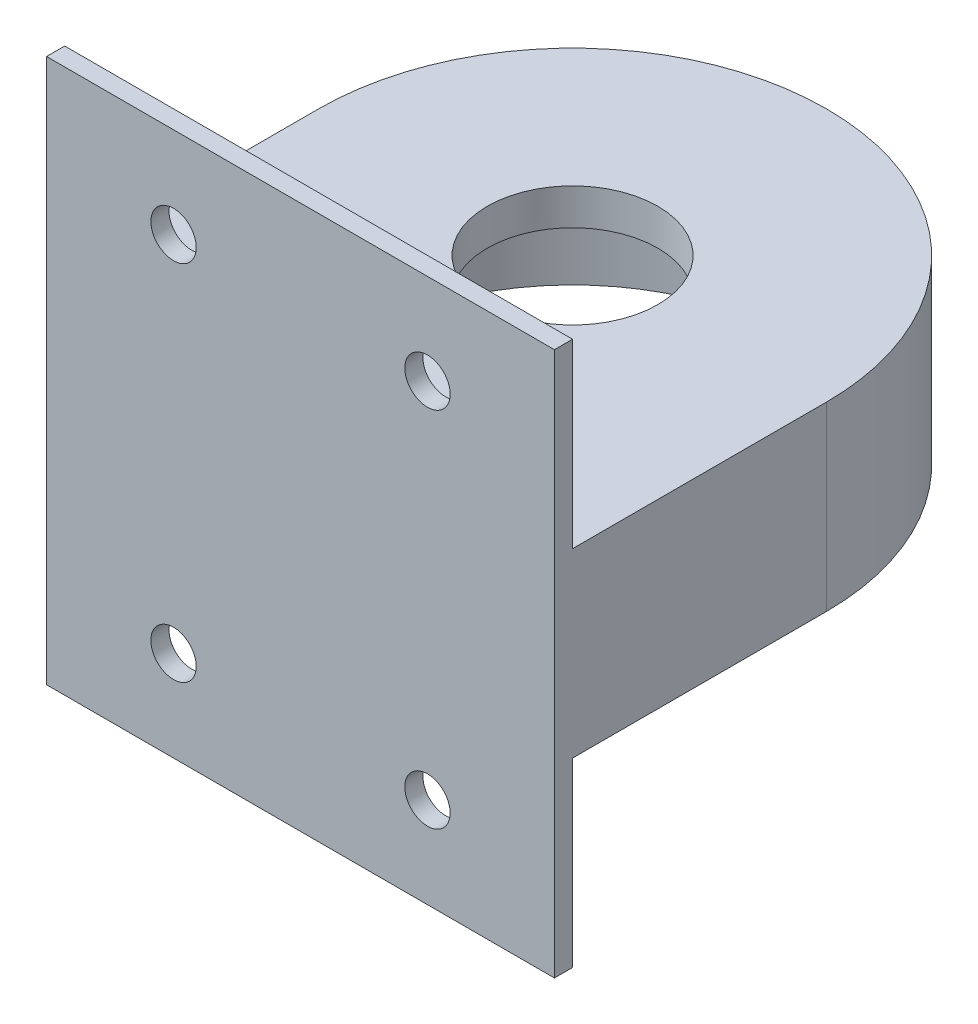
SolidWorks part; units mm, degrees
ref_plane "Front Plane" through (0, 0, 0) normal (0, 0, 1) x (1, 0, 0)
ref_plane "Top Plane" through (0, 0, 0) normal (0, 1, 0) x (1, 0, 0)
ref_plane "Right Plane" through (0, 0, 0) normal (1, 0, 0) x (0, 0, -1)
sketch "Sketch1" plane through (0, 0, 0) normal (0, 1, 0) x (1, 0, 0)
  line L2 (0, 0) -> (0, 1.2382)
  line L3 (0, 1.2382) -> (-28, 1.2382)
  line L4 (-28, 0) -> (-28, 1.2382)
  line L5 (-28, 29.2382) -> (0, 29.2382)
  line L6 (-28, 29.2382) -> (-28, 1.2382)
  line L7 (-28, 1.2382) -> (0, 1.2382)
  line L8 (0, 29.2382) -> (0, 1.2382)
  circle A1 centre (-14, 15.2382) radius 14
  circle A2 centre (-14, 15.2382) radius 4.7
  dimension "D1" = 9.4
  dimension "D2" = 28
extrude "Boss-Extrude1" add sketch "Sketch1" along normal blind 10 contours L4 L2 L3 L7 | A1 L3 L8 | A1 L6 L7 | A1 A2 region at (-3.1272, 0, -4.3654) region at (-24.8728, 0, -4.3654) region at (-23.6195, 0, -5.6187)
sketch "Sketch2" plane through (0, 0, -1.2382) normal (0, 0, 1) x (1, 0, 0)
  line L0 (-28, 5) -> (0, 5) construction
  line L1 (-28, 20) -> (0, 20)
  line L2 (-28, 20) -> (-28, -10)
  line L3 (-28, -10) -> (0, -10)
  line L4 (0, 20) -> (0, -10)
  line L5 (-14, -10) -> (-14, 20) construction
  line L6 (-28, 0) -> (0, 10) construction
  line L7 (-28, 10) -> (-28, 0) construction
  point P12 (-14, 5)
  point P13 (-14, 5)
  dimension "D1" = 30
extrude "Boss-Extrude2" add sketch "Sketch2" along normal blind 1
hole_wizard "Tap Drill for M3x0.5 Tap1" positions "Sketch3" profile "Sketch4" hole size "M3x0.5" standard "ANSI Metric" end condition through all
sketch "Sketch3" plane through (0, 0, -1.2382) normal (0, 0, -1) x (-1, 0, 0)
  line L0 (0, -5) -> (28, -5) construction
  line L1 (0, -10) -> (0, 0) construction
  line L2 (28, 0) -> (28, -10) construction
  line L5 (0, 15) -> (28, 15) construction
  line L6 (0, 10) -> (0, 20) construction
  line L7 (28, 20) -> (28, 10) construction
  line L10 (14, -10) -> (14, 20) construction
  line L11 (28, -10) -> (0, -10) construction
  line L12 (0, 20) -> (28, 20) construction
  line L13 (0, -10) -> (14, 0) construction
  line L14 (0, 0) -> (28, 0) construction
  line L16 (14, 10) -> (28, 20) construction
  line L17 (28, 10) -> (0, 10) construction
  line L20 (7, -5) -> (7, 15) construction
  line L21 (21, 15) -> (21, -5) construction
  point P0 (7, 15)
  point P2 (21, 15)
  point P4 (7, -5)
  point P6 (21, -5)
sketch "Sketch4" plane through (-7, 15, -1.2382) normal (1, 0, 0) x (0, 1, 0)
  line L0 (0, 0) -> (0, 1)
  line L1 (0, 1) -> (1.25, 1)
  line L2 (1.25, 1) -> (1.25, 0)
  line L5 (1.25, 0) -> (0, 0)
  line L11 (0, -6.35) -> (0, 107.95) construction
  dimension "Thru Hole Dia." = 2.5
  dimension "Thru Hole Depth" = 1
sketch "Sketch5" plane through (0, 0, 0) normal (0, -1, 0) x (1, 0, 0)
  circle A0 centre (-14, -15.2382) radius 12.15
  circle M6 centre (-14, -15.2382) radius 4.7
  dimension "D1" = 24.3
extrude "Cut-Extrude1" cut sketch "Sketch5" against normal blind 8 contours A0 M6 region at (-25.8063, 0, -15.2382)
sketch "Sketch8" plane through (0, 0, -1.2382) normal (0, 0, -1) x (-1, 0, 0)
  line L0 (7, 15) -> (7, 20) construction
  line L1 (0, 20) -> (28, 20) construction
  line L2 (7, 15) -> (0, 15) construction
  line L3 (0, 10) -> (0, 20) construction
